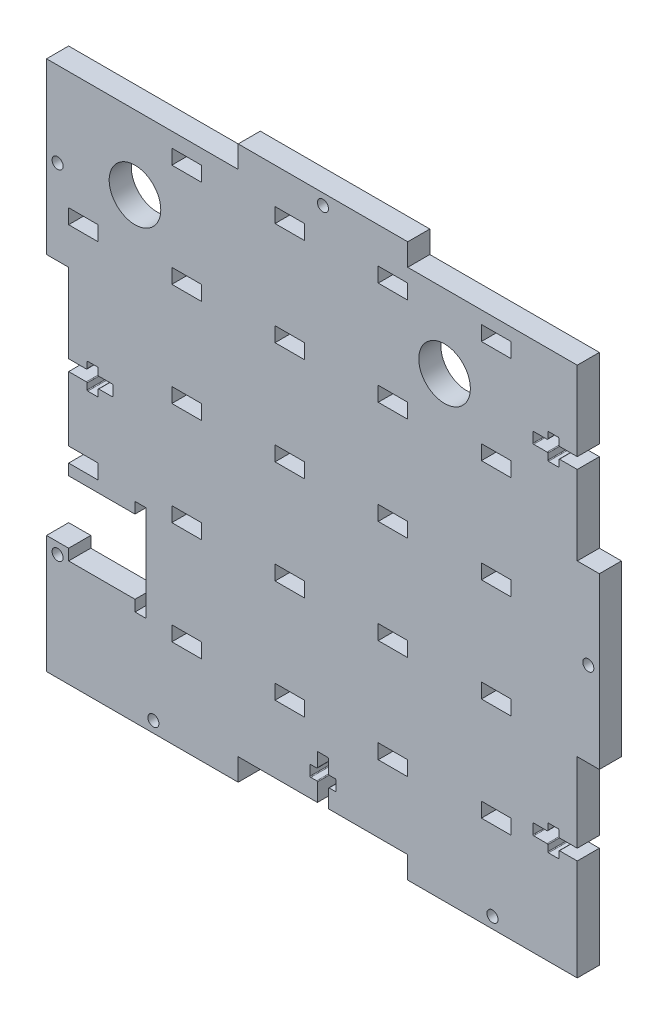
SolidWorks part; units mm, degrees
ref_plane "Front Plane" through (0, 0, 0) normal (0, 0, 1) x (1, 0, 0)
ref_plane "Top Plane" through (0, 0, 0) normal (0, 1, 0) x (1, 0, 0)
ref_plane "Right Plane" through (0, 0, 0) normal (1, 0, 0) x (0, 0, -1)
sketch "Sketch1" plane through (0, 0, 0) normal (0, 0, 1) x (1, 0, 0)
  line L0 (-69, 69) -> (-23, 69)
  line L5 (-75, -75) -> (75, -75) construction
  line L6 (-75, -75) -> (-75, 75) construction
  line L7 (-75, 75) -> (75, 75) construction
  line L8 (75, -75) -> (75, 75) construction
  line L9 (75, 23) -> (69, 23)
  line L10 (69, -23) -> (75, -23)
  line L11 (-69, -69) -> (69, -69) construction
  line L12 (-69, -69) -> (-69, 69) construction
  line L13 (-69, 69) -> (69, 69) construction
  line L14 (69, -69) -> (69, 69) construction
  line L15 (-69, -69) -> (69, 69) construction
  line L16 (69, -69) -> (69, -23)
  line L17 (-23, 69) -> (-23, 75)
  line L18 (-23, 75) -> (23, 75)
  line L19 (23, 75) -> (23, 69)
  line L20 (23, 69) -> (69, 69)
  line L21 (75, -23) -> (75, 23)
  line L22 (69, 23) -> (69, 69)
  line L23 (-75, 23) -> (-69, 23)
  line L24 (-69, 69) -> (-75, 69)
  line L25 (-75, 69) -> (-75, 23)
  line L26 (69, -69) -> (69, -75)
  line L27 (69, -75) -> (23, -75)
  line L28 (23, -75) -> (23, -69)
  line L29 (23, -69) -> (-23, -69)
  line L30 (-23, -69) -> (-23, -75)
  line L31 (-23, -75) -> (-69, -75)
  line L32 (-69, -75) -> (-69, -69) construction
  line L33 (-69, 23) -> (-69, -23)
  line L34 (-69, -23) -> (-75, -23)
  line L35 (-75, -23) -> (-75, -69)
  line L36 (-75, -69) -> (-69, -69) construction
  line L37 (-46, 69) -> (-46, -75) construction
  line L38 (-69, 69) -> (69, -69) construction
  line L39 (-75, -75) -> (-69, -75)
  line L40 (-75, -75) -> (-75, -69)
  point P0 (0, 0)
  point P6 (-7, -7)
  point P26 (0, -75)
  point P27 (-75, 0)
  dimension "D1" = 150
  dimension "D2" = 150
  dimension "D5" = 46
  dimension "D3" = 6
  dimension "D6" = 6
  dimension "D7" = 6
extrude "Box Side" add sketch "Sketch1" along normal blind 6
sketch "Sketch2" plane through (0, 0, 6) normal (0, 0, 1) x (1, 0, 0)
  line L0 (23, 72) -> (-23, 72) construction
  line L1 (23, 75) -> (23, 69) construction
  line L2 (-23, 69) -> (-23, 75) construction
  line L3 (-46, 69) -> (-46, -75) construction
  line L5 (0, 75) -> (0, 69) construction
  line L6 (-23, 75) -> (23, 75) construction
  line L7 (-69, 69) -> (69, 69) construction
  line L16 (-46, 69) -> (-46, -75) construction
  line L21 (0, -69) -> (0, 69) construction
  line L35 (-69, 69) -> (-23, 69) construction
  line L36 (-44.5, 69) -> (-44.5, 64.2) construction
  line L37 (-44.3, 64) -> (-42.7, 64) construction
  line L38 (-42.5, 63.8) -> (-42.5, 61.2) construction
  line L39 (-42.7, 61) -> (-44.3, 61) construction
  line L40 (-44.5, 60.8) -> (-44.5, 57.2) construction
  line L46 (-44.7, 57) -> (-47.3, 57) construction
  line L48 (-44.5, 69) -> (-47.5, 69) construction
  line L51 (-47.5, 60.8) -> (-47.5, 57.2) construction
  line L52 (-49.3, 61) -> (-47.7, 61) construction
  line L53 (-49.5, 63.8) -> (-49.5, 61.2) construction
  line L54 (-47.7, 64) -> (-49.3, 64) construction
  line L55 (-47.5, 69) -> (-47.5, 64.2) construction
  line L56 (47.5, 69) -> (47.5, 64.2) construction
  line L57 (47.7, 64) -> (49.3, 64) construction
  line L58 (49.5, 63.8) -> (49.5, 61.2) construction
  line L59 (49.3, 61) -> (47.7, 61) construction
  line L60 (47.5, 60.8) -> (47.5, 57.2) construction
  line L61 (44.5, 69) -> (47.5, 69) construction
  line L62 (44.7, 57) -> (47.3, 57) construction
  line L63 (44.5, 60.8) -> (44.5, 57.2) construction
  line L64 (42.7, 61) -> (44.3, 61) construction
  line L65 (42.5, 63.8) -> (42.5, 61.2) construction
  line L66 (44.3, 64) -> (42.7, 64) construction
  line L67 (44.5, 69) -> (44.5, 64.2) construction
  line L68 (-69, -69) -> (69, 69) construction
  line L69 (-69, -69) -> (69, 69) construction
  line L70 (75, 0) -> (69, 0) construction
  line L71 (72, 23) -> (72, -23) construction
  line L72 (69, 44.5) -> (64.2, 44.5)
  line L73 (64, 44.3) -> (64, 42.7)
  line L74 (63.8, 42.5) -> (61.2, 42.5)
  line L75 (61, 42.7) -> (61, 44.3)
  line L76 (60.8, 44.5) -> (57.2, 44.5)
  line L77 (57, 44.7) -> (57, 47.3)
  line L78 (69, 44.5) -> (69, 47.5)
  line L79 (60.8, 47.5) -> (57.2, 47.5)
  line L80 (61, 49.3) -> (61, 47.7)
  line L81 (63.8, 49.5) -> (61.2, 49.5)
  line L82 (64, 47.7) -> (64, 49.3)
  line L83 (69, 47.5) -> (64.2, 47.5)
  line L84 (69, -47.5) -> (64.2, -47.5)
  line L85 (64, -47.7) -> (64, -49.3)
  line L86 (63.8, -49.5) -> (61.2, -49.5)
  line L87 (61, -49.3) -> (61, -47.7)
  line L88 (60.8, -47.5) -> (57.2, -47.5)
  line L89 (69, -44.5) -> (69, -47.5)
  line L90 (57, -44.7) -> (57, -47.3)
  line L91 (60.8, -44.5) -> (57.2, -44.5)
  line L92 (61, -42.7) -> (61, -44.3)
  line L93 (63.8, -42.5) -> (61.2, -42.5)
  line L94 (64, -44.3) -> (64, -42.7)
  line L95 (69, -44.5) -> (64.2, -44.5)
  line L120 (-69, 69) -> (69, -69) construction
  line L121 (-69, 69) -> (69, -69) construction
  line L122 (-1.5, -69) -> (1.5, -69)
  line L123 (-23, -69) -> (23, -69) construction
  line L124 (1.5, -69) -> (1.5, -64.2)
  line L125 (1.7, -64) -> (3.3, -64)
  line L126 (3.5, -63.8) -> (3.5, -61.2)
  line L127 (3.3, -61) -> (1.7, -61)
  line L128 (1.5, -60.8) -> (1.5, -57.2)
  line L129 (1.3, -57) -> (-1.3, -57)
  line L130 (-1.5, -60.8) -> (-1.5, -57.2)
  line L131 (-3.3, -61) -> (-1.7, -61)
  line L132 (-3.5, -63.8) -> (-3.5, -61.2)
  line L133 (-1.7, -64) -> (-3.3, -64)
  line L134 (-1.5, -69) -> (-1.5, -64.2)
  line L135 (-69, -1.5) -> (-64.2, -1.5)
  line L136 (-64, -1.7) -> (-64, -3.3)
  line L137 (-63.8, -3.5) -> (-61.2, -3.5)
  line L138 (-61, -3.3) -> (-61, -1.7)
  line L139 (-60.8, -1.5) -> (-57.2, -1.5)
  line L140 (-57, 1.3) -> (-57, -1.3)
  line L141 (-60.8, 1.5) -> (-57.2, 1.5)
  line L142 (-61, 3.3) -> (-61, 1.7)
  line L143 (-63.8, 3.5) -> (-61.2, 3.5)
  line L144 (-64, 1.7) -> (-64, 3.3)
  line L145 (-69, 1.5) -> (-64.2, 1.5)
  line L146 (-69, -1.5) -> (-69, 1.5)
  line L147 (-69, -72) -> (-23, -72) construction
  line L148 (-23, 69) -> (-75, 69) construction
  line L149 (-23, -75) -> (-23, -69) construction
  line L150 (-69, -69) -> (-69, -75) construction
  line L151 (-75, -75) -> (-23, -75) construction
  circle A0 centre (0, 72) radius 1.5
  arc A1 (-44.5, 57.2) -> (-44.7, 57) centre (-44.7, 57.2) cw construction
  arc A2 (-44.3, 61) -> (-44.5, 60.8) centre (-44.3, 60.8) ccw construction
  arc A3 (-42.5, 61.2) -> (-42.7, 61) centre (-42.7, 61.2) cw construction
  arc A4 (-42.7, 64) -> (-42.5, 63.8) centre (-42.7, 63.8) cw construction
  arc A5 (-44.5, 64.2) -> (-44.3, 64) centre (-44.3, 64.2) ccw construction
  arc A6 (-47.5, 64.2) -> (-47.7, 64) centre (-47.7, 64.2) cw construction
  arc A7 (-49.3, 64) -> (-49.5, 63.8) centre (-49.3, 63.8) ccw construction
  arc A8 (-49.5, 61.2) -> (-49.3, 61) centre (-49.3, 61.2) ccw construction
  arc A9 (-47.7, 61) -> (-47.5, 60.8) centre (-47.7, 60.8) cw construction
  arc A10 (-47.5, 57.2) -> (-47.3, 57) centre (-47.3, 57.2) ccw construction
  arc A11 (47.5, 57.2) -> (47.3, 57) centre (47.3, 57.2) cw construction
  arc A12 (47.7, 61) -> (47.5, 60.8) centre (47.7, 60.8) ccw construction
  arc A13 (49.5, 61.2) -> (49.3, 61) centre (49.3, 61.2) cw construction
  arc A14 (49.3, 64) -> (49.5, 63.8) centre (49.3, 63.8) cw construction
  arc A15 (47.5, 64.2) -> (47.7, 64) centre (47.7, 64.2) ccw construction
  arc A16 (44.5, 64.2) -> (44.3, 64) centre (44.3, 64.2) cw construction
  arc A17 (42.7, 64) -> (42.5, 63.8) centre (42.7, 63.8) ccw construction
  arc A18 (42.5, 61.2) -> (42.7, 61) centre (42.7, 61.2) ccw construction
  arc A19 (44.3, 61) -> (44.5, 60.8) centre (44.3, 60.8) cw construction
  arc A20 (44.5, 57.2) -> (44.7, 57) centre (44.7, 57.2) ccw construction
  arc A21 (57.2, 44.5) -> (57, 44.7) centre (57.2, 44.7) cw
  arc A22 (61, 44.3) -> (60.8, 44.5) centre (60.8, 44.3) ccw
  arc A23 (61.2, 42.5) -> (61, 42.7) centre (61.2, 42.7) cw
  arc A24 (64, 42.7) -> (63.8, 42.5) centre (63.8, 42.7) cw
  arc A25 (64.2, 44.5) -> (64, 44.3) centre (64.2, 44.3) ccw
  arc A26 (64.2, 47.5) -> (64, 47.7) centre (64.2, 47.7) cw
  arc A27 (64, 49.3) -> (63.8, 49.5) centre (63.8, 49.3) ccw
  arc A28 (61.2, 49.5) -> (61, 49.3) centre (61.2, 49.3) ccw
  arc A29 (61, 47.7) -> (60.8, 47.5) centre (60.8, 47.7) cw
  arc A30 (57.2, 47.5) -> (57, 47.3) centre (57.2, 47.3) ccw
  arc A31 (57.2, -47.5) -> (57, -47.3) centre (57.2, -47.3) cw
  arc A32 (61, -47.7) -> (60.8, -47.5) centre (60.8, -47.7) ccw
  arc A33 (61.2, -49.5) -> (61, -49.3) centre (61.2, -49.3) cw
  arc A34 (64, -49.3) -> (63.8, -49.5) centre (63.8, -49.3) cw
  arc A35 (64.2, -47.5) -> (64, -47.7) centre (64.2, -47.7) ccw
  arc A36 (64.2, -44.5) -> (64, -44.3) centre (64.2, -44.3) cw
  arc A37 (64, -42.7) -> (63.8, -42.5) centre (63.8, -42.7) ccw
  arc A38 (61.2, -42.5) -> (61, -42.7) centre (61.2, -42.7) ccw
  arc A39 (61, -44.3) -> (60.8, -44.5) centre (60.8, -44.3) cw
  arc A40 (57.2, -44.5) -> (57, -44.7) centre (57.2, -44.7) ccw
  circle A41 centre (72, 0) radius 1.5
  arc A62 (1.5, -57.2) -> (1.3, -57) centre (1.3, -57.2) ccw
  arc A63 (1.7, -61) -> (1.5, -60.8) centre (1.7, -60.8) cw
  arc A64 (3.5, -61.2) -> (3.3, -61) centre (3.3, -61.2) ccw
  arc A65 (3.3, -64) -> (3.5, -63.8) centre (3.3, -63.8) ccw
  arc A66 (1.5, -64.2) -> (1.7, -64) centre (1.7, -64.2) cw
  arc A67 (-1.5, -64.2) -> (-1.7, -64) centre (-1.7, -64.2) ccw
  arc A68 (-3.3, -64) -> (-3.5, -63.8) centre (-3.3, -63.8) cw
  arc A69 (-3.5, -61.2) -> (-3.3, -61) centre (-3.3, -61.2) cw
  arc A70 (-1.7, -61) -> (-1.5, -60.8) centre (-1.7, -60.8) ccw
  arc A71 (-1.5, -57.2) -> (-1.3, -57) centre (-1.3, -57.2) cw
  arc A72 (-57.2, -1.5) -> (-57, -1.3) centre (-57.2, -1.3) ccw
  arc A73 (-61, -1.7) -> (-60.8, -1.5) centre (-60.8, -1.7) cw
  arc A74 (-61.2, -3.5) -> (-61, -3.3) centre (-61.2, -3.3) ccw
  arc A75 (-64, -3.3) -> (-63.8, -3.5) centre (-63.8, -3.3) ccw
  arc A76 (-64.2, -1.5) -> (-64, -1.7) centre (-64.2, -1.7) cw
  arc A77 (-64.2, 1.5) -> (-64, 1.7) centre (-64.2, 1.7) ccw
  arc A78 (-64, 3.3) -> (-63.8, 3.5) centre (-63.8, 3.3) cw
  arc A79 (-61.2, 3.5) -> (-61, 3.3) centre (-61.2, 3.3) cw
  arc A80 (-61, 1.7) -> (-60.8, 1.5) centre (-60.8, 1.7) ccw
  arc A81 (-57.2, 1.5) -> (-57, 1.3) centre (-57.2, 1.3) cw
  circle A82 centre (-46, -72) radius 1.5
  circle A83 centre (46, -72) radius 1.5
  circle A84 centre (-72, 46) radius 1.5
  circle A85 centre (-72, -46) radius 1.5
  point P6 (0, 72)
  point P38 (0, 0)
  point P56 (-46, 57)
  point P88 (46, 57)
  point P161 (57, 46)
  point P162 (57, -46)
  point P198 (0, -57)
  point P231 (-57, 0)
  point P234 (-42.5, 62.5)
  dimension "D1" = 3
  dimension "D2" = 0.2
  dimension "D8" = 0.2
  dimension "D14" = 3
  dimension "D4" = 3
  dimension "D7" = 1.5
  dimension "D10" = 3
  dimension "D12" = 1.5
  dimension "D9" = 12
  dimension "D11" = 5
  dimension "D13" = 7
  dimension "D3" = 12
  dimension "D5" = 7
  dimension "D6" = 5
extrude "Screw Cut-outs" cut sketch "Sketch2" against normal through all
sketch "Sketch3" plane through (0, 0, 6) normal (0, 0, 1) x (1, 0, 0)
  line L0 (-75, -75) -> (-23, -75) construction
  line L1 (-75, -49) -> (-48, -49)
  line L2 (-75, -49) -> (-75, -23)
  line L3 (-75, -23) -> (-48, -23)
  line L4 (-48, -49) -> (-48, -23)
  line L5 (-75, -23) -> (-75, -75) construction
  line L6 (-75, -46) -> (-48, -46)
  line L7 (-75, -26) -> (-48, -26)
  line L9 (-75, -26) -> (-69, -26)
  line L10 (-75, -26) -> (-75, -29)
  line L11 (-75, -29) -> (-69, -29)
  line L12 (-69, -26) -> (-69, -29)
  line L13 (-75, -46) -> (-69, -46)
  line L14 (-75, -46) -> (-75, -43)
  line L15 (-75, -43) -> (-69, -43)
  line L16 (-69, -46) -> (-69, -43)
  line L17 (-69, -26) -> (-75, -26)
  line L18 (-69, -26) -> (-69, -23)
  line L19 (-69, -23) -> (-75, -23)
  line L20 (-75, -26) -> (-75, -23)
  line L25 (-48, -23) -> (-51, -23)
  line L26 (-48, -23) -> (-48, -26)
  line L27 (-48, -26) -> (-51, -26)
  line L28 (-51, -23) -> (-51, -26)
  line L29 (-48, -46) -> (-51, -46)
  line L30 (-48, -46) -> (-48, -49)
  line L31 (-48, -49) -> (-51, -49)
  line L32 (-51, -46) -> (-51, -49)
  dimension "D1" = 26
  dimension "D2" = 27
  dimension "D3" = 26
  dimension "D4" = 20
  dimension "D5" = 3
  dimension "D6" = 3
  dimension "D7" = 6
  dimension "D8" = 3
  dimension "D9" = 3
extrude "Cut-Extrude1" cut sketch "Sketch3" against normal through all contours L7 L2 L6 L4 | L10 L9 L12 L11 | L18 L17 L20 L19 | L26 L25 L28 L27 | L30 L29 L32 L31 region at (-60.75, -36, 6)
sketch "Sketch4" plane through (0, 0, 6) normal (0, 0, 1) x (1, 0, 0)
  line L0 (-33, 65) -> (-33, 61)
  line L1 (-69, 65) -> (-61, 65) construction
  line L2 (-69, 65) -> (-69, 61) construction
  line L3 (-69, 61) -> (-61, 61) construction
  line L4 (-61, 65) -> (-61, 61) construction
  line L5 (-65, 63) -> (-37, 63) construction
  line L6 (-65, 63) -> (-65, 35) construction
  line L7 (-65, 35) -> (-37, 35) construction
  line L8 (-37, 63) -> (-37, 35) construction
  line L9 (-65, 63) -> (-37, 35) construction
  line L10 (-65, 35) -> (-37, 63) construction
  line L11 (-41, 65) -> (-33, 65)
  line L12 (-41, 65) -> (-41, 61)
  line L13 (-41, 61) -> (-33, 61)
  line L14 (-33, 37) -> (-33, 33)
  line L15 (-41, 37) -> (-33, 37)
  line L16 (-41, 37) -> (-41, 33)
  line L17 (-41, 33) -> (-33, 33)
  line L18 (-61, 37) -> (-61, 33)
  line L19 (-69, 37) -> (-61, 37)
  line L20 (-69, 37) -> (-69, 33)
  line L21 (-69, 33) -> (-61, 33)
  line L22 (-23, 69) -> (-75, 69) construction
  line L23 (-75, 69) -> (-75, 23) construction
  line L24 (15, 33.2836) -> (23, 33.2836)
  line L25 (15, 37.2836) -> (23, 37.2836)
  line L26 (15, 37.2836) -> (15, 33.2836)
  line L27 (23, 37.2836) -> (23, 33.2836)
  line L28 (-5, 37.2836) -> (-5, 33.2836)
  line L29 (-13, 33.2836) -> (-5, 33.2836)
  line L30 (-13, 37.2836) -> (-13, 33.2836)
  line L31 (-13, 37.2836) -> (-5, 37.2836)
  line L32 (-13, 61.2836) -> (-5, 61.2836)
  line L33 (-13, 65.2836) -> (-13, 61.2836)
  line L34 (-13, 65.2836) -> (-5, 65.2836)
  line L35 (-5, 65.2836) -> (-5, 61.2836)
  line L36 (23, 65.2836) -> (23, 61.2836)
  line L37 (15, 61.2836) -> (23, 61.2836)
  line L38 (15, 65.2836) -> (23, 65.2836)
  line L39 (15, 65.2836) -> (15, 61.2836)
  line L44 (51, 37.5671) -> (51, 33.5671)
  line L45 (43, 33.5671) -> (51, 33.5671)
  line L46 (43, 37.5671) -> (43, 33.5671)
  line L47 (43, 37.5671) -> (51, 37.5671)
  line L48 (43, 61.5671) -> (51, 61.5671)
  line L49 (43, 65.5671) -> (43, 61.5671)
  line L50 (43, 65.5671) -> (51, 65.5671)
  line L51 (51, 65.5671) -> (51, 61.5671)
  line L56 (15, -22.7164) -> (23, -22.7164)
  line L57 (15, -18.7164) -> (23, -18.7164)
  line L58 (15, -18.7164) -> (15, -22.7164)
  line L59 (23, -18.7164) -> (23, -22.7164)
  line L60 (-5, -18.7164) -> (-5, -22.7164)
  line L61 (-13, -22.7164) -> (-5, -22.7164)
  line L62 (-13, -18.7164) -> (-13, -22.7164)
  line L63 (-13, -18.7164) -> (-5, -18.7164)
  line L64 (-13, 5.2836) -> (-5, 5.2836)
  line L65 (-13, 9.2836) -> (-13, 5.2836)
  line L66 (-13, 9.2836) -> (-5, 9.2836)
  line L67 (-5, 9.2836) -> (-5, 5.2836)
  line L68 (23, 9.2836) -> (23, 5.2836)
  line L69 (15, 5.2836) -> (23, 5.2836)
  line L70 (15, 9.2836) -> (23, 9.2836)
  line L71 (15, 9.2836) -> (15, 5.2836)
  line L76 (51, -18.4329) -> (51, -22.4329)
  line L77 (43, -22.4329) -> (51, -22.4329)
  line L78 (43, -18.4329) -> (43, -22.4329)
  line L79 (43, -18.4329) -> (51, -18.4329)
  line L80 (43, 5.5671) -> (51, 5.5671)
  line L81 (43, 9.5671) -> (43, 5.5671)
  line L82 (43, 9.5671) -> (51, 9.5671)
  line L83 (51, 9.5671) -> (51, 5.5671)
  line L96 (-13, -50.7164) -> (-5, -50.7164)
  line L97 (-13, -46.7164) -> (-13, -50.7164)
  line L98 (-13, -46.7164) -> (-5, -46.7164)
  line L99 (-5, -46.7164) -> (-5, -50.7164)
  line L100 (23, -46.7164) -> (23, -50.7164)
  line L101 (15, -50.7164) -> (23, -50.7164)
  line L102 (15, -46.7164) -> (23, -46.7164)
  line L103 (15, -46.7164) -> (15, -50.7164)
  line L112 (43, -50.4329) -> (51, -50.4329)
  line L113 (43, -46.4329) -> (43, -50.4329)
  line L114 (43, -46.4329) -> (51, -46.4329)
  line L115 (51, -46.4329) -> (51, -50.4329)
  line L120 (-41, -23) -> (-33, -23)
  line L121 (-41, -19) -> (-33, -19)
  line L122 (-41, -19) -> (-41, -23)
  line L123 (-33, -19) -> (-33, -23)
  line L124 (-61, -19) -> (-61, -23)
  line L125 (-69, -23) -> (-61, -23)
  line L126 (-69, -19) -> (-69, -23)
  line L127 (-69, -19) -> (-61, -19)
  line L128 (-69, 5) -> (-61, 5) construction
  line L129 (-69, 9) -> (-69, 5) construction
  line L130 (-69, 9) -> (-61, 9) construction
  line L131 (-61, 9) -> (-61, 5) construction
  line L132 (-33, 9) -> (-33, 5)
  line L133 (-41, 5) -> (-33, 5)
  line L134 (-41, 9) -> (-33, 9)
  line L135 (-41, 9) -> (-41, 5)
  line L144 (-69, -51) -> (-61, -51) construction
  line L145 (-69, -47) -> (-69, -51) construction
  line L146 (-69, -47) -> (-61, -47) construction
  line L147 (-61, -47) -> (-61, -51) construction
  line L148 (-33, -47) -> (-33, -51)
  line L149 (-41, -51) -> (-33, -51)
  line L150 (-41, -47) -> (-33, -47)
  line L151 (-41, -47) -> (-41, -51)
  line L152 (15, -78.7164) -> (23, -78.7164) [skipped]
  line L153 (15, -74.7164) -> (23, -74.7164) [skipped]
  line L154 (15, -74.7164) -> (15, -78.7164) [skipped]
  line L155 (23, -74.7164) -> (23, -78.7164) [skipped]
  line L156 (-5, -74.7164) -> (-5, -78.7164) [skipped]
  line L157 (-13, -78.7164) -> (-5, -78.7164) [skipped]
  line L158 (-13, -74.7164) -> (-13, -78.7164) [skipped]
  line L159 (-13, -74.7164) -> (-5, -74.7164) [skipped]
  line L160 (71, -78.4329) -> (79, -78.4329) [skipped]
  line L161 (71, -74.4329) -> (79, -74.4329) [skipped]
  line L162 (71, -74.4329) -> (71, -78.4329) [skipped]
  line L163 (79, -74.4329) -> (79, -78.4329) [skipped]
  line L164 (51, -74.4329) -> (51, -78.4329) [skipped]
  line L165 (43, -78.4329) -> (51, -78.4329) [skipped]
  line L166 (43, -74.4329) -> (43, -78.4329) [skipped]
  line L167 (43, -74.4329) -> (51, -74.4329) [skipped]
  line L168 (-41, -79) -> (-33, -79) [skipped]
  line L169 (-41, -75) -> (-33, -75) [skipped]
  line L170 (-41, -75) -> (-41, -79) [skipped]
  line L171 (-33, -75) -> (-33, -79) [skipped]
  line L172 (-61, -75) -> (-61, -79) [skipped]
  line L173 (-69, -79) -> (-61, -79) [skipped]
  line L174 (-69, -75) -> (-69, -79) [skipped]
  line L175 (-69, -75) -> (-61, -75) [skipped]
  line L176 (71, 33.5671) -> (79, 33.5671) [skipped]
  line L177 (71, 37.5671) -> (79, 37.5671) [skipped]
  line L178 (71, 37.5671) -> (71, 33.5671) [skipped]
  line L179 (79, 37.5671) -> (79, 33.5671) [skipped]
  line L180 (79, 65.5671) -> (79, 61.5671) [skipped]
  line L181 (71, 61.5671) -> (79, 61.5671) [skipped]
  line L182 (71, 65.5671) -> (79, 65.5671) [skipped]
  line L183 (71, 65.5671) -> (71, 61.5671) [skipped]
  line L184 (71, -22.4329) -> (79, -22.4329) [skipped]
  line L185 (71, -18.4329) -> (79, -18.4329) [skipped]
  line L186 (71, -18.4329) -> (71, -22.4329) [skipped]
  line L187 (79, -18.4329) -> (79, -22.4329) [skipped]
  line L188 (79, 9.5671) -> (79, 5.5671) [skipped]
  line L189 (71, 5.5671) -> (79, 5.5671) [skipped]
  line L190 (71, 9.5671) -> (79, 9.5671) [skipped]
  line L191 (71, 9.5671) -> (71, 5.5671) [skipped]
  line L192 (79, -46.4329) -> (79, -50.4329) [skipped]
  line L193 (71, -50.4329) -> (79, -50.4329) [skipped]
  line L194 (71, -46.4329) -> (79, -46.4329) [skipped]
  line L195 (71, -46.4329) -> (71, -50.4329) [skipped]
  circle A0 centre (-65, 63) radius 2 construction
  point P6 (-65, 61)
  point P7 (-69, 35)
  point P8 (-65, 33)
  point P12 (-51, 49)
  point P13 (-37, 33)
  point P33 (-37, 61)
  point P41 (-65, 37)
  dimension "D1" = 8
  dimension "D2" = 4
  dimension "D3" = 2
  dimension "D5" = 28
  dimension "D6" = 6
  dimension "D7" = 10
  dimension "D10" = 20
  dimension "D11" = 24
  dimension "D4" = 2
  dimension "D8" = 3
  dimension "D9" = 3
extrude "Cut-Extrude2" cut sketch "Sketch4" against normal through all
sketch "Sketch5" plane through (0, 0, 6) normal (0, 0, 1) x (1, 0, 0)
  line L0 (-61, 37) -> (-69, 37) construction
  line L1 (-61, 33) -> (-61, 37) construction
  line L3 (23, 33.2836) -> (23, 37.2836) construction
  line L4 (23, 37.2836) -> (15, 37.2836) construction
  circle A0 centre (-51, 49) radius 7
  circle A1 centre (33, 49) radius 7
  point P2 (-65, 37)
  point P3 (-61, 35)
  point P6 (-65, 35)
  point P9 (19, 37.2836)
  point P10 (23, 35.2836)
  dimension "D3" = 14
  dimension "D5" = 14
  dimension "D1" = 14
  dimension "D2" = 14
  dimension "D4" = 14
extrude "Cut-Extrude3" cut sketch "Sketch5" against normal through all
equation "\"filletRadius\"=0.2"
equation "\"D8@Sketch2\"=\"filletRadius\""
equation "\"D2@Sketch2\"=\"filletRadius\""
equation "\"fingerWidth\"= 46"
equation "\"D5@Sketch1\"=\"fingerWidth\""
equation "\"wallThickness\"= 6"
equation "\"D3@Sketch1\" = \"wallThickness\""
equation "\"D6@Sketch1\" = \"wallThickness\""
equation "\"D7@Sketch1\" = \"wallThickness\""
equation "\"D1@Box Side\" = \"wallThickness\""
equation "\"M3\"= 3"
equation "\"D14@Sketch2\"=\"M3\""
equation "\"D1@Sketch2\"=\"M3\""
equation "\"D12@Sketch2\"=\"M3\"/2"
equation "\"nutThickness\"=3"
equation "\"D10@Sketch2\" = \"nutThickness\""
equation "\"boltLength\"= 12"
equation "\"D9@Sketch2\" = \"boltLength\""
equation "\"distanceToNut\"= 5"
equation "\"D11@Sketch2\" = \"distanceToNut\""
equation "\"D13@Sketch2\" = \"nutWidth\""
equation "\"D7@Sketch2\"=\"M3\"/2"
equation "\"D4@Sketch2\" = \"nutThickness\""
equation "\"D3@Sketch2\" = \"boltLength\""
equation "\"D5@Sketch2\" = \"nutWidth\""
equation "\"D6@Sketch2\" = \"distanceToNut\""
equation "\"sideLength\"=150"
equation "\"D1@Sketch1\"=\"sideLength\""
equation "\"D2@Sketch1\"=\"sideLength\""
equation "\"nutWidth\"=7"
